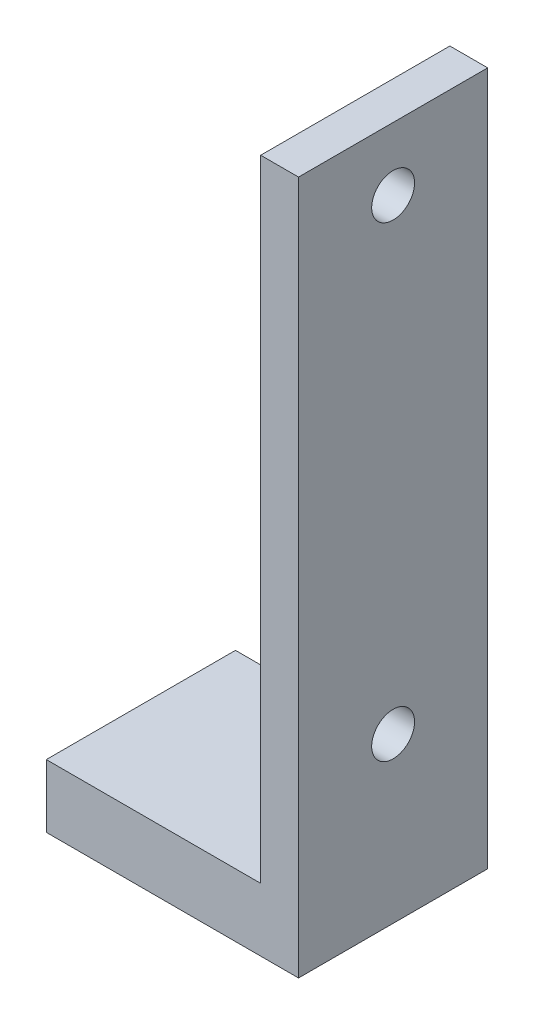
SolidWorks part; units mm, degrees
ref_plane "Front Plane" through (0, 0, 0) normal (0, 0, 1) x (1, 0, 0)
ref_plane "Top Plane" through (0, 0, 0) normal (0, 1, 0) x (1, 0, 0)
ref_plane "Right Plane" through (0, 0, 0) normal (1, 0, 0) x (0, 0, -1)
sketch "Sketch2" plane through (0, 0, 0) normal (0, 1, 0) x (1, 0, 0)
  line L1 (-10, -7.5) -> (10, -7.5)
  line L2 (-10, -7.5) -> (-10, 7.5)
  line L3 (-10, 7.5) -> (10, 7.5)
  line L4 (10, -7.5) -> (10, 7.5)
  line L5 (-10, -7.5) -> (10, 7.5) construction
  line L6 (-10, 7.5) -> (10, -7.5) construction
  point P0 (0, 0)
  dimension "D1" = 15
  dimension "D2" = 20
extrude "Axle Base" add sketch "Sketch2" against normal blind 5
sketch "Sketch3" plane through (0, 0, 0) normal (1, 0, 0) x (0, 0, -1)
  line L0 (7.5, -5) -> (7.5, 0) construction
  line L1 (-7.5, 0) -> (7.5, 0)
  line L2 (-7.5, 0) -> (-7.5, 50)
  line L3 (-7.5, 50) -> (7.5, 50)
  line L4 (7.5, 0) -> (7.5, 50)
  dimension "D1" = 50
extrude "Sensor Mount" add sketch "Sketch3" against normal blind 3 from surface starting at face at (10, -2.5, 0)
hole_wizard "Sensor Holes" positions "Sketch4" profile "Sketch5" hole size "M3" standard "ANSI Metric"
sketch "Sketch4" plane through (10, 0, 0) normal (1, 0, 0) x (0, 0, -1)
  line L1 (7.5, 50) -> (-7.5, 50) construction
  line L2 (0, 0) -> (0, 50) construction
  line L3 (-7.5, 0) -> (7.5, 0) construction
  point P0 (0, 8)
  point P2 (0, 45)
  dimension "D1" = 37
  dimension "D2" = 5
sketch "Sketch5" plane through (10, 8, 0) normal (0, 1, 0) x (0, 0, -1)
  line L0 (0, 0) -> (0, 5.0215)
  line L1 (0, 5.0215) -> (1.7, 4)
  line L2 (1.7, 4) -> (1.7, 0)
  line L5 (1.7, 0) -> (0, 0)
  line L10 (0, 5.0215) -> (-1.7, 4) construction
  line L11 (0, -6.35) -> (0, 107.95) construction
  dimension "Hole Dia." = 3.4
  dimension "Hole Depth" = 4
  dimension "Drill Angle" = 118
sketch "Sketch7" plane through (0, 0, 0) normal (0, 1, 0) x (1, 0, 0)
  circle A0 centre (0, 0) radius 2.975
  circle A1 centre (0, 0) radius 0.825
  dimension "D1" = 1.65
  dimension "D2" = 5.95
extrude "Axle Mount" cut sketch "Sketch7" along normal blind 3 from surface starting at face at (0, -5, 0)
equation "\"D1@Sketch7\"=1.85 - 0.2"
equation "\"D2@Sketch7\"=5.75+0.2"
